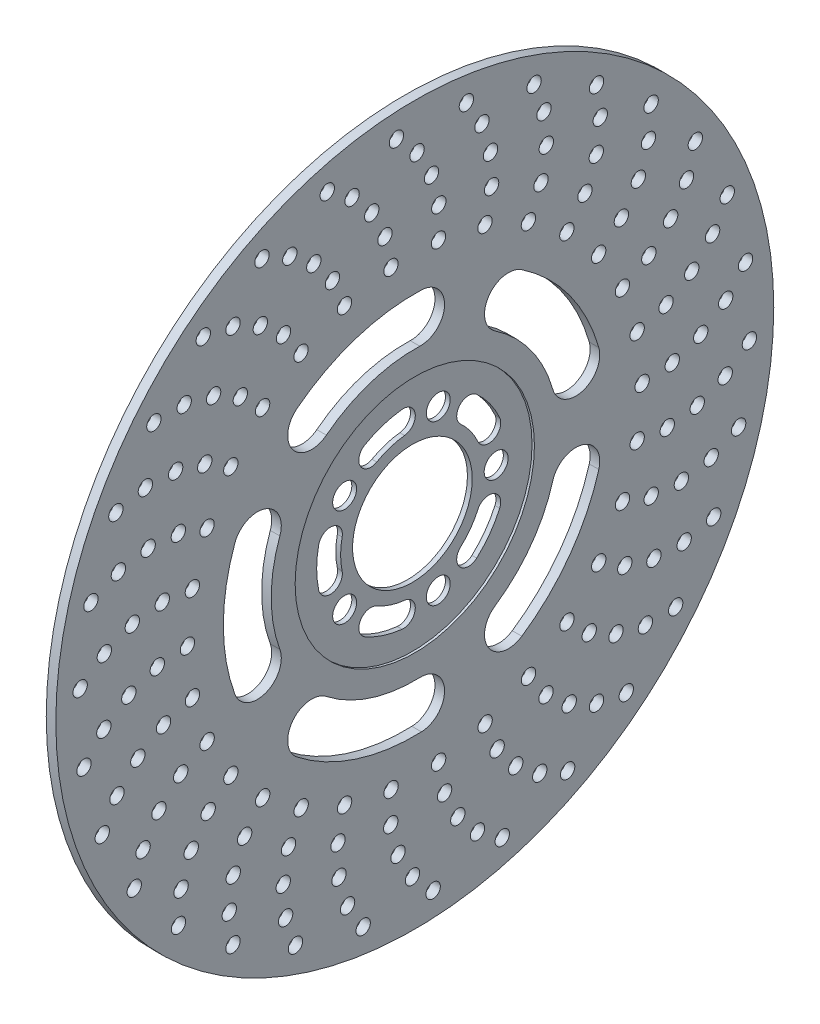
SolidWorks part; units mm, degrees
material "AISI 304"
ref_plane "Front Plane" through (0, 0, 0) normal (1, 0, 0) x (0, 1, 0)
ref_plane "Top Plane" through (0, 0, 0) normal (0, 0, 1) x (0, 1, 0)
ref_plane "Right Plane" through (0, 0, 0) normal (0, 1, 0) x (-1, 0, 0)
sketch "Sketch1" plane through (0, 0, 0) normal (1, 0, 0) x (0, 1, 0)
  line L0 (-112.8184, 0) -> (148.4018, 0) construction
  line L1 (0, 127.9014) -> (0, -119.9572) construction
  line L2 (0, 0) -> (-51.303, 140.9539) construction
  line L3 (0, 0) -> (45.5375, 125.1132) construction
  line L4 (0, 0) -> (-45.8638, 85.4882) construction
  line L5 (0, 0) -> (-78.8018, 78.8018) construction
  circle A0 centre (0, 0) radius 150
  circle A1 centre (0, 0) radius 50
  circle A3 centre (0, 0) radius 25
  circle A4 centre (0, -35) radius 5
  arc A5 (-40, 0) -> (40, 0) centre (0, 0) ccw
  arc A6 (6.1281, 29.3674) -> (-6.1281, 29.3674) centre (0, 0) ccw
  arc A7 (6.1281, 29.3674) -> (8.1708, 39.1566) centre (7.1495, 34.262) ccw
  arc A8 (-8.1708, 39.1566) -> (-6.1281, 29.3674) centre (-7.1495, 34.262) ccw
  arc A9 (-13.6808, 37.5877) -> (-40, 0) centre (0, 0) ccw construction
  arc A10 (8.1708, 39.1566) -> (-8.1708, 39.1566) centre (0, 0) ccw
  arc A11 (40, 0) -> (13.6808, 37.5877) centre (0, 0) ccw construction
  arc A12 (30, 0) -> (10.2606, 28.1908) centre (0, 0) ccw construction
  arc A13 (-30, 0) -> (30, 0) centre (0, 0) ccw
  arc A14 (-10.2606, 28.1908) -> (-30, 0) centre (0, 0) ccw construction
  arc A15 (-8.1708, 39.1566) -> (-13.6808, 37.5877) centre (0, 0) ccw construction
  arc A16 (13.6808, 37.5877) -> (8.1708, 39.1566) centre (0, 0) ccw construction
  arc A17 (10.2606, 28.1908) -> (6.1281, 29.3674) centre (0, 0) ccw construction
  arc A18 (-6.1281, 29.3674) -> (-10.2606, 28.1908) centre (0, 0) ccw construction
  arc A19 (-80, 0) -> (80, 0) centre (0, 0) ccw
  arc A20 (20.5212, 56.3816) -> (-20.5212, 56.3816) centre (0, 0) ccw
  arc A21 (-27.3616, 75.1754) -> (-20.5212, 56.3816) centre (-23.9414, 65.7785) ccw
  arc A23 (20.5212, 56.3816) -> (27.3616, 75.1754) centre (23.9414, 65.7785) ccw
  arc A24 (-27.3616, 75.1754) -> (-80, 0) centre (0, 0) ccw construction
  circle A25 centre (0, 0) radius 80 construction
  arc A26 (27.3616, 75.1754) -> (-27.3616, 75.1754) centre (0, 0) ccw
  arc A27 (80, 0) -> (27.3616, 75.1754) centre (0, 0) ccw construction
  arc A28 (-60, 0) -> (60, 0) centre (0, 0) ccw
  arc A29 (60, 0) -> (20.5212, 56.3816) centre (0, 0) ccw construction
  circle A30 centre (0, 0) radius 60 construction
  arc A31 (-20.5212, 56.3816) -> (-60, 0) centre (0, 0) ccw construction
  point P33 (57.3783, 17.5423)
  point P34 (76.5044, 23.3897)
  dimension "D1" = 300
  dimension "D2" = 100
  dimension "D3" = 50
  dimension "D5" = 10
  dimension "D6" = 80
  dimension "D7" = 30
  dimension "D8" = 20
  dimension "D10" = 160
  dimension "D12" = 45
  dimension "D4" = 35
  dimension "D9" = 20
  dimension "D11" = 20
extrude "Boss-Extrude1" add sketch "Sketch1" along normal mid plane 4 contours A0 | A1
extrude "Boss-Extrude2" add sketch "Sketch1<3>" along normal mid plane 2 contours A1 A10 A7 A6 A8 A4 A3 | A4 | A6 A8 A10 A7 region at (0, -48.5858, 0)
sketch "Sketch1<3>" plane through (0, 0, 0) normal (1, 0, 0) x (0, 1, 0) same geometry as "Sketch1"
extrude "Cut-Extrude1" cut sketch "Sketch1<4>" against normal through all both and the other way through all contours A7 A10 A8 A6 | A4 region at (0, 0, -35) region at (0, 0, 34.5801)
sketch "Sketch1<4>" plane through (0, 0, 0) normal (1, 0, 0) x (0, 1, 0) same geometry as "Sketch1"
pattern_circular "CirPattern1" count 5 over 360 about axis through (1, 0, 0) along (1, 0, 0) of "Cut-Extrude1"
sketch "Sketch2" plane through (2, 0, 0) normal (1, 0, 0) x (0, 1, 0)
  line L0 (0, 103.6913) -> (0, -78.0626) construction
  line L1 (-110.3359, 0) -> (113.646, 0) construction
  circle A1 centre (0, 0) radius 140 construction
  circle A2 centre (0, 0) radius 95 construction
  arc A3 (0, 96.6353) -> (-22.2413, 138.222) centre (-50, 96.6353) ccw
  circle A4 centre (-22.2413, 138.222) radius 3
  arc A5 (-1.6009, 84.0843) -> (-12.691, 129.9225) centre (-50, 96.6353) ccw
  circle A6 centre (-12.691, 129.9225) radius 3
  arc A7 (-6.3011, 72.337) -> (-5.5298, 119.4914) centre (-50, 96.6353) ccw
  circle A8 centre (-5.5298, 119.4914) radius 3
  arc A9 (-13.7996, 62.1457) -> (-1.2163, 107.5966) centre (-50, 96.6353) ccw
  circle A10 centre (-1.2163, 107.5966) radius 3
  arc A11 (-23.6163, 54.163) -> (-0.0267, 95) centre (-50, 96.6353) ccw
  circle A12 centre (-0.0267, 95) radius 3
  dimension "D2" = 280
  dimension "D4" = 190
  dimension "D5" = 50
  dimension "D6" = 6
  dimension "D7" = 5
  dimension "D8" = 11.0286
extrude "Cut-Extrude2" cut sketch "Sketch2" against normal through all both and the other way through all contours A4 | A5 A6 A3 | A3 A6 A5 | A7 A8 A5 | A5 A8 A7 | A9 A10 A7 | A7 A10 A9 | A11 A12 A9 A3 | A12 A11 A3 A9 region at (2, -1.3154, 95.0422) region at (2, 1.2295, 94.9589) region at (2, -25.0181, 139.1093) region at (2, -13.653, 129.0641) region at (2, -11.7531, 130.7593) region at (2, -6.6765, 118.902) region at (2, -4.4119, 120.0659) region at (2, -2.4743, 107.314) region at (2, 0.01, 107.8722)
pattern_circular "CirPattern2" count 30 over 360 about axis through (2, 0, 0) along (1, 0, 0) of "Cut-Extrude2"
extrude "Cut-Extrude3" cut sketch "Sketch1<5>" against normal through all both and the other way through all contours A23 A26 A21 A20 region at (0, 0, 67.9039)
sketch "Sketch1<5>" plane through (0, 0, 0) normal (1, 0, 0) x (0, 1, 0) same geometry as "Sketch1"
pattern_circular "CirPattern3" count 5 over 360 about axis through (1, 0, 0) along (1, 0, 0) of "Cut-Extrude3"
